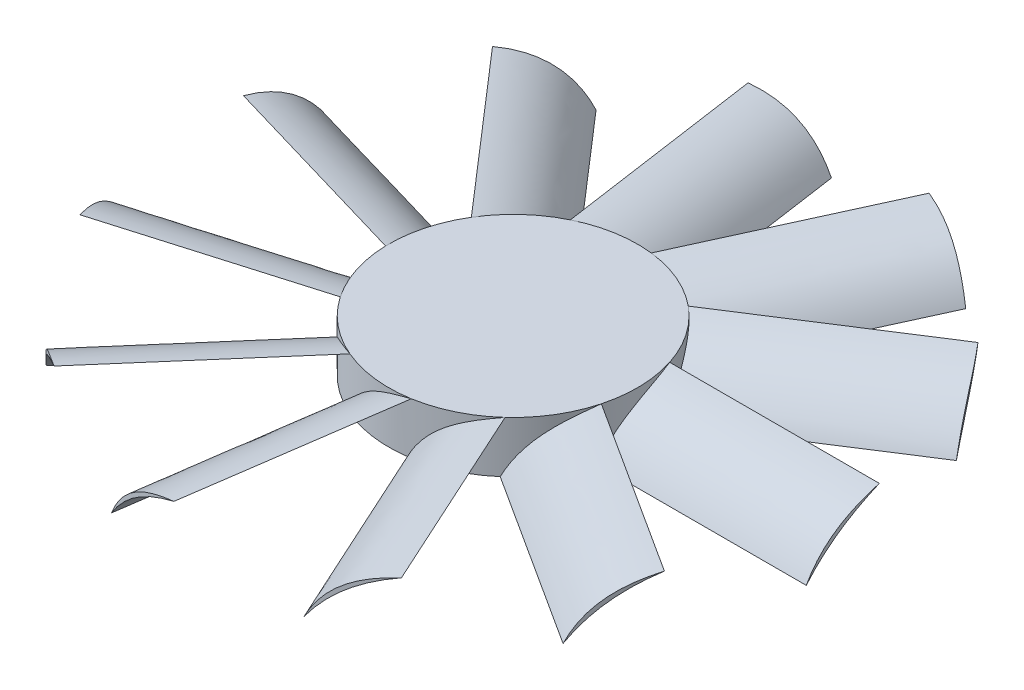
SolidWorks part; units mm, degrees
ref_plane "Front Plane" through (0, 0, 0) normal (0, 0, 1) x (1, 0, 0)
ref_plane "Top Plane" through (0, 0, 0) normal (0, 1, 0) x (1, 0, 0)
ref_plane "Right Plane" through (0, 0, 0) normal (1, 0, 0) x (0, 0, -1)
sketch "Sketch1" plane through (0, 0, 0) normal (0, 1, 0) x (1, 0, 0)
  circle A0 centre (0, 0) radius 11.5
  circle A1 centre (0, 0) radius 14.5
extrude "Boss-Extrude1" add sketch "Sketch1" along normal blind 6
sketch "Sketch3" plane through (0, 6, 0) normal (0, 1, 0) x (1, 0, 0)
  circle A0 centre (0, 0) radius 11.5
extrude "Boss-Extrude3" add sketch "Sketch3" against normal blind 1
sketch "Sketch5" plane through (0, 0, 0) normal (1, 0, 0) x (0, 0, -1)
  line L7 (-14.5, 0) -> (14.5, 0) construction
  line L8 (14.5, 6) -> (-14.5, 6) construction
  spline S0 degree 2 poles (4.4394, 6) (-0.8949, 4.5874) (-4.1155, 0) knots 0 0 0 1 1 1
  spline S1 degree 2 poles (4.4394, 6) (-1.6684, 5.1664) (-4.1155, 0) knots 0 0 0 1 1 1
extrude "Boss-Extrude4" add sketch "Sketch5" along normal blind 48
pattern_circular "CirPattern1" count 11 every 32.727 about axis through (0, 6, 0) along (0, 1, 0) of "Boss-Extrude4"
sketch "Sketch6" plane through (0, 0, 0) normal (0, -1, 0) x (1, 0, 0)
  circle A0 centre (0, 0) radius 11.5
extrude "Cut-Extrude1" cut sketch "Sketch6" against normal blind 5
sketch "Sketch7" plane through (0, 6, 0) normal (0, 1, 0) x (1, 0, 0)
  circle A0 centre (0, 0) radius 38.5
  circle A1 centre (0, 0) radius 49.8911
extrude "Cut-Extrude2" cut sketch "Sketch7" against normal blind 48
sketch "Sketch8" plane through (0, 5, 0) normal (0, -1, 0) x (1, 0, 0)
  circle A0 centre (0, 0) radius 1
extrude "Boss-Extrude5" add sketch "Sketch8" along normal blind 8.5
sketch "Sketch10" plane through (0, 0, 0) normal (1, 0, 0) x (0, 0, -1)
  line L0 (-1, -3.5) -> (1, -3.5) construction
  line L1 (-1, -2.5) -> (-0.75, -2.5)
  line L2 (-1, -2.5) -> (-1, -2.2)
  line L3 (-1, -2.2) -> (-0.75, -2.2)
  line L4 (-0.75, -2.5) -> (-0.75, -2.2)
  dimension "D1" = 0.25
  dimension "D2" = 0.3
  dimension "D3" = 1
ref_axis "Axis1" through (0, -3.5, 0) along (0, 1, 0)
revolve "Cut-Revolve1" cut sketch "Sketch10" angle 360 about axis through (0, -3.5, 0) along (0, 1, 0)
chamfer "Chamfer1" distance 0.5 angle 45 1 edges at (0, -3.5, -1)
